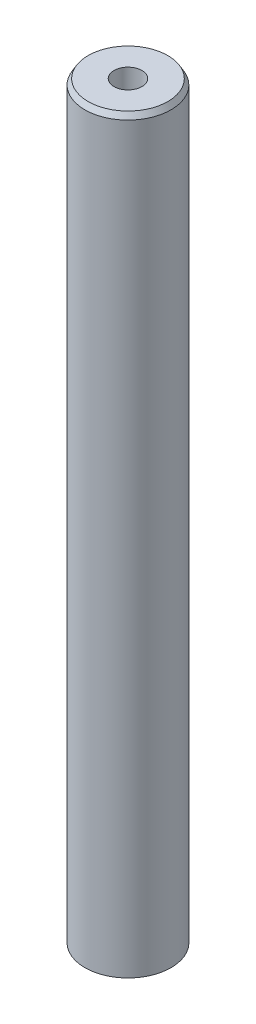
SolidWorks part; units mm, degrees
ref_plane "Front Plane" through (0, 0, 0) normal (0, 0, 1) x (1, 0, 0)
ref_plane "Top Plane" through (0, 0, 0) normal (0, 1, 0) x (1, 0, 0)
ref_plane "Right Plane" through (0, 0, 0) normal (1, 0, 0) x (0, 0, -1)
sketch "Sketch1" plane through (0, 0, 0) normal (0, 1, 0) x (1, 0, 0)
  circle A0 centre (0, 0) radius 5
  dimension "SHAFT_OD" = 10
extrude "Boss-Extrude1" add sketch "Sketch1" along normal blind 87.2702
sketch "Sketch2" plane through (0, 0, 0) normal (0, 1, 0) x (1, 0, 0)
  circle A0 centre (0, 0) radius 1.6229
  dimension "BORE_D" = 3.2459
extrude "Cut-Extrude1" cut sketch "Sketch2" along normal through all
chamfer "Chamfer1" distance 0.646 angle 30 2 edges at (0, 87.2702, 5) (0, 0, 5) first distance on face at (0, 87.2702, 5) first distance on face at (0, 0, 1.6229)
